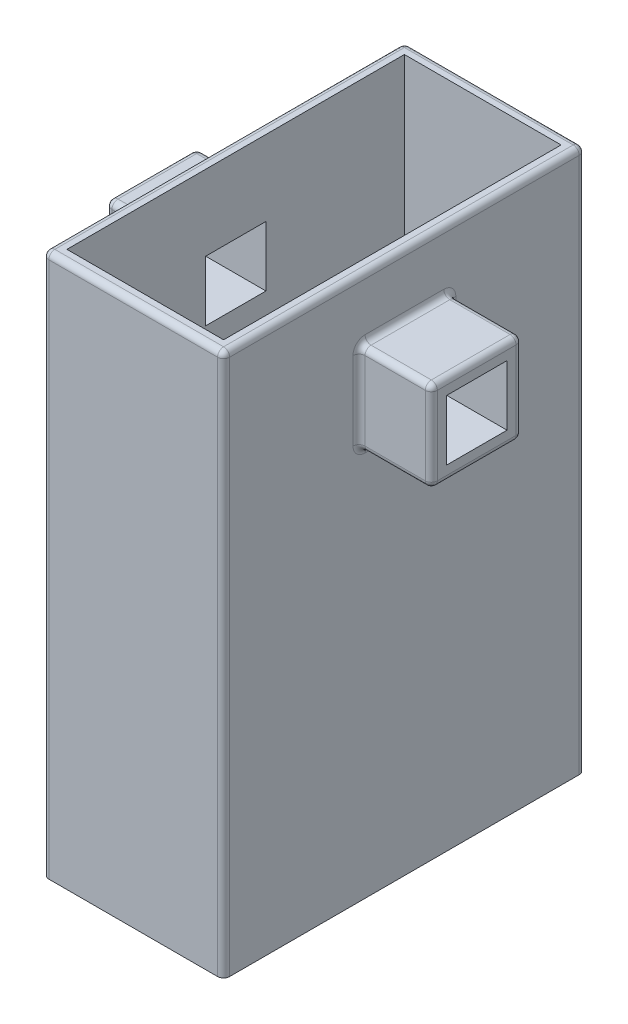
SolidWorks part; units mm, degrees
ref_plane "Front Plane" through (0, 0, 0) normal (0, 0, 1) x (1, 0, 0)
ref_plane "Top Plane" through (0, 0, 0) normal (0, 1, 0) x (1, 0, 0)
ref_plane "Right Plane" through (0, 0, 0) normal (1, 0, 0) x (0, 0, -1)
sketch "Sketch1" plane through (0, 0, 0) normal (0, 0, 1) x (1, 0, 0)
  line L1 (0, 0) -> (300, 0)
  line L2 (0, 0) -> (0, -900)
  line L3 (0, -900) -> (300, -900)
  line L4 (300, 0) -> (300, -900)
  dimension "D1" = 900
  dimension "D2" = 300
extrude "Boss-Extrude1" add sketch "Sketch1" against normal blind 600
sketch "Sketch4" plane through (300, 0, 0) normal (1, 0, 0) x (0, 0, -1)
  line L0 (300, 0) -> (300, -487.7609) construction
  line L1 (600, 0) -> (0, 0) construction
  line L3 (224.7, -100) -> (375.3, -100)
  line L4 (224.7, -100) -> (224.7, -250)
  line L5 (224.7, -250) -> (375.3, -250)
  line L6 (375.3, -250) -> (375.3, -100)
  point P4 (300, -100)
extrude "Boss-Extrude3" add sketch "Sketch4" along normal blind 120
sketch "Sketch6" plane through (0, 0, 0) normal (-1, 0, 0) x (0, 0, 1)
  line L0 (-300, 0) -> (-300, -381.6529) construction
  line L1 (-600, 0) -> (0, 0) construction
  line L2 (-375.3, -100) -> (-224.7, -100)
  line L3 (-375.3, -100) -> (-375.3, -250)
  line L4 (-375.3, -250) -> (-224.7, -250)
  line L5 (-224.7, -250) -> (-224.7, -100)
  point P4 (-300, -100)
  dimension "D1" = 150.6
  dimension "D2" = 150
extrude "Boss-Extrude4" add sketch "Sketch6" along normal blind 120
sketch "Sketch7" plane through (-120, 0, 0) normal (-1, 0, 0) x (0, 0, 1)
  line L0 (-375.3, -100) -> (-224.7, -250) construction
  line L1 (-350.3, -125) -> (-249.7, -225) construction
  line L2 (-350.3, -125) -> (-249.7, -125)
  line L3 (-350.3, -125) -> (-350.3, -225)
  line L4 (-350.3, -225) -> (-249.7, -225)
  line L5 (-249.7, -125) -> (-249.7, -225)
  point P8 (-300, -175)
  point P9 (-300, -175)
  dimension "D1" = 100.6
  dimension "D2" = 100
sketch "Sketch8" plane through (0, -900, 0) normal (0, -1, 0) x (1, 0, 0)
  line L0 (0, 0) -> (300, 0) construction
  line L1 (20, -20) -> (280, -20)
  line L2 (20, -20) -> (20, -580)
  line L3 (20, -580) -> (280, -580)
  line L4 (280, -20) -> (280, -580)
  line L5 (0, -600) -> (0, 0) construction
  line L6 (300, -600) -> (300, 0) construction
  line L7 (0, -600) -> (300, -600) construction
  dimension "D1" = 20
  dimension "D2" = 20
  dimension "D3" = 20
  dimension "D4" = 20
fillet "Fillet1" radius 10 3 edges at (0, 0, -300) (0, -450, -600) (300, -450, -600)
fillet "Fillet2" radius 10 12 edges at (0, -250, -300) (0, -175, -375.3) (0, -175, -224.7) (-60, -250, -224.7) (-60, -250, -375.3) (-120, -250, -300) (-120, -175, -375.3) (-60, -100, -375.3) (-60, -100, -224.7) (0, -100, -300) (-120, -175, -224.7) (-120, -100, -300)
fillet "Fillet3" radius 10 12 edges at (300, -250, -300) (360, -250, -375.3) (420, -175, -375.3) (360, -100, -375.3) (300, -175, -375.3) (360, -100, -224.7) (420, -175, -224.7) (360, -250, -224.7) (300, -175, -224.7) (420, -250, -300) (420, -100, -300) (300, -100, -300)
fillet "Fillet5" radius 10 4 edges at (2.9289, -2.9289, -597.0711) (150, 0, -600) (297.0711, 0, -597.0711) (300, 0, -295)
fillet "Fillet6" radius 10 5 edges at (0, -455, 0) (2.9289, -2.9289, 0) (150, 0, 0) (297.0711, -2.9289, 0) (300, -455, 0)
extrude "Cut-Extrude1" cut sketch "Sketch8" against normal through all
extrude "Cut-Extrude2" cut sketch "Sketch7" against normal through all
